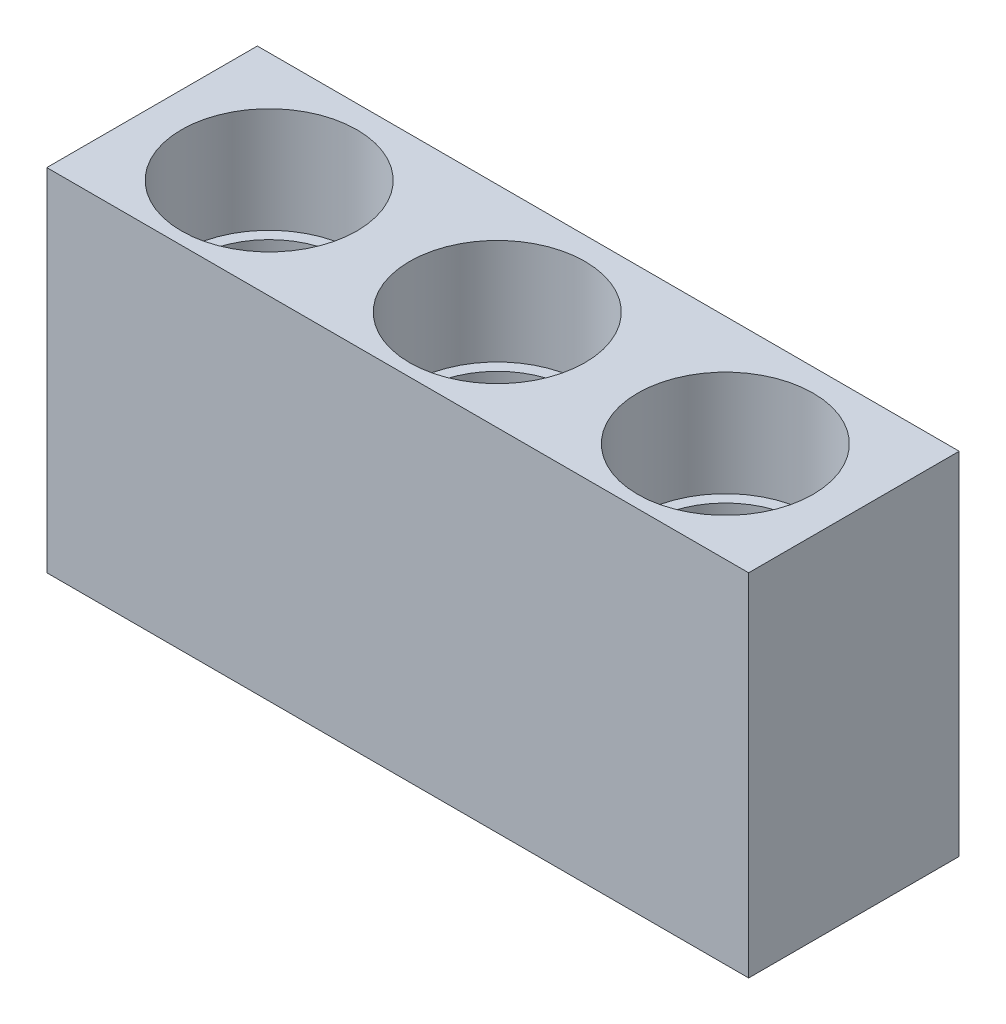
SolidWorks part; units mm, degrees
ref_plane "Front Plane" through (0, 0, 0) normal (0, 0, 1) x (1, 0, 0)
ref_plane "Top Plane" through (0, 0, 0) normal (0, 1, 0) x (1, 0, 0)
ref_plane "Right Plane" through (0, 0, 0) normal (1, 0, 0) x (0, 0, -1)
sketch "Sketch1" plane through (0, 0, 0) normal (0, 1, 0) x (1, 0, 0)
  line L0 (-6.5163, 2.8531) -> (6.5163, 2.8531) construction
  line L5 (-8.25, 0) -> (8.25, 0) construction
  line L6 (-10, -6) -> (10, -6)
  line L7 (-10, -6) -> (-10, 6)
  line L8 (-10, 6) -> (10, 6)
  line L9 (10, -6) -> (10, 6)
  line L10 (-10, -6) -> (10, 6) construction
  line L11 (-10, 6) -> (10, -6) construction
  line L12 (-6.5163, -2.8531) -> (6.5163, -2.8531) construction
  line L13 (-10, 0) -> (10, 0)
  circle A18 centre (-6.5163, 2.8531) radius 2.175
  circle A19 centre (0, 2.8531) radius 2.175
  circle A20 centre (6.5163, 2.8531) radius 2.175
  circle A21 centre (-6.5163, 2.8531) radius 2.5
  circle A22 centre (0, 2.8531) radius 2.5
  circle A23 centre (6.5163, 2.8531) radius 2.5
  point P3 (0, 2.8531)
  point P11 (0, 0)
  point P20 (0, 0)
  point P23 (0, 0)
  point P24 (0, 0)
  point P25 (6.5163, 2.8531)
  dimension "D1" = 4.35
  dimension "D2" = 5
  dimension "D3" = 2.8531
  dimension "D4" = 12
  dimension "D5" = 20
extrude "Boss-Extrude1" add sketch "Sketch1" along normal mid plane 10 contours L7 L13 L9 L8 A23 A22 A21 | A22 A19 | A19 | A20 | A23 A20 | A21 region at (-9.7912, 0, -3) region at (0, 0, -2.8531) region at (6.5163, 0, -2.8531) region at (-2.4293, 0, -2.8531) region at (4.0871, 0, -2.8531)
extrude "Cut-Extrude1" cut sketch "Sketch1<4>" against normal blind 3 from surface contours A21 A18 | A18 region at (-6.5163, 0, -2.8531) region at (-8.9456, 0, -2.8531) starting at face at (0, 5, -3)
sketch "Sketch1<4>" plane through (0, 0, 0) normal (0, 1, 0) x (1, 0, 0) same geometry as "Sketch1"
extrude "Cut-Extrude2" cut sketch "Sketch1<5>" against normal blind 5 from surface contours A18 starting at face at (-6.5163, 2, -0.3531)
sketch "Sketch1<5>" plane through (0, 0, 0) normal (0, 1, 0) x (1, 0, 0) same geometry as "Sketch1"
pattern_linear "LPattern1" count 3 spacing 6.5 along (1, 0, 0) of "Cut-Extrude1", "Cut-Extrude2"
